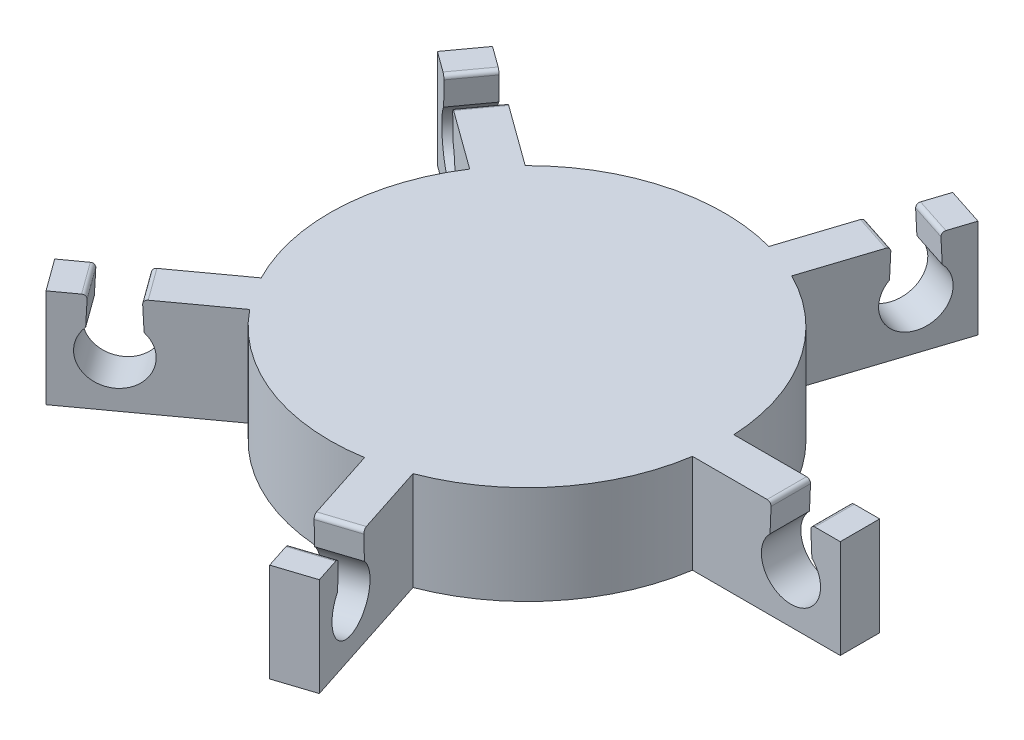
SolidWorks part; units mm, degrees
note: '?' marks a value the reader was unsure of.
ref_plane "Plan de face" through (0, 0, 0) normal (0, 0, 1) x (1, 0, 0)
ref_plane "Plan de dessus" through (0, 0, 0) normal (0, 1, 0) x (1, 0, 0)
ref_plane "Plan de droite" through (0, 0, 0) normal (1, 0, 0) x (0, 0, -1)
sketch "Esquisse1" plane through (0, 0, 0) normal (0, 1, 0) x (1, 0, 0)
  circle A0 centre (0, 0) radius 10
  dimension "D1" = 20
extrude "BASE" add sketch "Esquisse1" against normal blind 5
sketch "Esquisse2" plane through (0, 0, 0) normal (0, 1, 0) x (1, 0, 0)
  line L0 (9.3808, -1.5) -> (17.3808, -1.5)
  line L1 (17.3808, -1.5) -> (17.3808, 0.5)
  line L2 (17.3808, 0.5) -> (9.4868, 0.5)
  arc A1 (9.3808, -1.5) -> (9.4868, 0.5) centre (0, 0) ccw
  dimension "D1" = 8
  dimension "D2" = 19
  dimension "D3" = 2
extrude "BOSS - BALEINE" add sketch "Esquisse2" against normal blind 5 contours A1 L0 L1 L2
sketch "Esquisse3" plane through (0, 0, 1.5) normal (0, 0, 1) x (1, 0, 0)
  line L0 (12.3808, 0) -> (17.3808, -5) construction
  line L1 (17.3808, -5) -> (17.3808, -2.5) construction
  line L3 (17.3808, -5) -> (17.3808, 0) construction
  line L4 (17.3808, -2.5) -> (14.8808, -2.5) construction
  line L5 (14.8808, -2.5) -> (17.3808, 0) construction
  line L6 (13.8202, -1.4393) -> (13.8808, 0)
  line L7 (9.8869, 0) -> (17.3808, 0) construction
  line L8 (15.9415, -1.4393) -> (15.8808, 0)
  arc A0 (13.8202, -1.4393) -> (15.9415, -1.4393) centre (14.8808, -2.5) ccw
  point P4 (14.8808, 0)
  dimension "D1" = 3
  dimension "D2" = 5
  dimension "D3" = 1
  dimension "D4" = 1
extrude "VIDE - BALEINE" cut sketch "Esquisse3" against normal up to surface (3 mm away)
ref_axis "AXE CYLINDRE" through (0, -5, 0) along (0, 1, 0)?
pattern_circular "REP - SUPPORT BALEINE" count 5 over 360 about axis through (0, 0, 0) along (0, 1, 0) of "BOSS - BALEINE", "VIDE - BALEINE"
fillet "CONGE BALEINE" radius 0.2 10 edges at (4.7649, 0, -13.0469) (5.383, 0, -14.9491) (-10.9359, 0, -8.5635) (-12.554, 0, -9.739) (-13.1418, 0, 8.93) (-11.5237, 0, 7.7544) (3.8139, 0, 13.356) (4.4319, 0, 15.2581) (15.8808, 0, 0.5) (13.8808, 0, 0.5)
